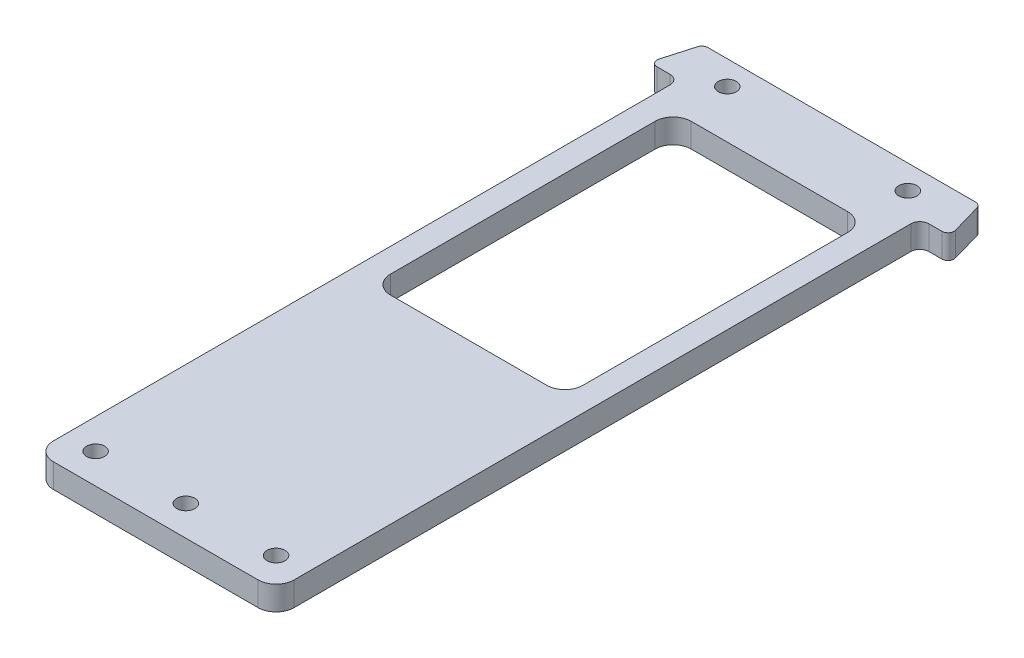
SolidWorks part; units mm, degrees
material "1060 Alloy"
ref_plane "Front Plane" through (0, 0, 0) normal (0, 0, 1) x (1, 0, 0)
ref_plane "Top Plane" through (0, 0, 0) normal (0, 1, 0) x (1, 0, 0)
ref_plane "Right Plane" through (0, 0, 0) normal (1, 0, 0) x (0, 0, -1)
sketch "Sketch1" plane through (0, 0, 0) normal (0, 1, 0) x (1, 0, 0)
  line L1 (0, 0) -> (40, 0)
  line L3 (0, 114) -> (40, 114)
  line L5 (4, 102) -> (36, 102)
  line L6 (4, 102) -> (4, 52)
  line L7 (4, 52) -> (36, 52)
  line L8 (36, 102) -> (36, 52)
  line L9 (40, 114) -> (40, 0)
  line L11 (0, 114) -> (0, 0)
  line L12 (20, 5) -> (20, 0) construction
  circle A0 centre (5, 5) radius 1.5
  circle A1 centre (35, 5) radius 1.5
  circle A2 centre (20, 5) radius 1.5
  circle A3 centre (5, 110) radius 1.5
  circle A4 centre (35, 110) radius 1.5
  dimension "D7" = 3
  dimension "D12" = 3
  dimension "D2" = 32
  dimension "D3" = 50
  dimension "D4" = 4
  dimension "D5" = 12
  dimension "D6" = 52
  dimension "D8" = 5
  dimension "D9" = 5
  dimension "D10" = 5
  dimension "D14" = 4
  dimension "D15" = 4
  dimension "D16" = 5
  dimension "D17" = 5
extrude "Boss-Extrude1" add sketch "Sketch1" along normal blind 4
fillet "Fillet1" radius 3 4 edges at (36, 2, -52) (4, 2, -52) (36, 2, -102) (4, 2, -102)
sketch "Sketch2" plane through (0, 4, 0) normal (0, 1, 0) x (1, 0, 0)
  line L0 (0, 114) -> (-3, 114)
  line L1 (-3, 114) -> (-5, 107)
  line L2 (-5, 107) -> (0, 107)
  line L4 (0, 107) -> (0, 114)
  line L5 (40, 114) -> (43, 114)
  line L6 (43, 114) -> (45, 107)
  line L7 (45, 107) -> (40, 107)
  line L9 (40, 107) -> (40, 114)
  line L10 (40, 114) -> (0, 114) construction
  line L11 (0, 114) -> (0, 0) construction
  dimension "D1" = 7
  dimension "D2" = 5
  dimension "D3" = 3
extrude "Boss-Extrude2" add sketch "Sketch2" against normal up to surface (4 mm away) up to face at (5, 0, -108.5)
fillet "Fillet2" radius 1 4 edges at (43, 2, -114) (45, 2, -107) (-5, 2, -107) (-3, 2, -114)
fillet "Fillet4" radius 3 2 edges at (40, 2, 0) (0, 2, 0)
fillet "Fillet5" radius 1.5 2 edges
